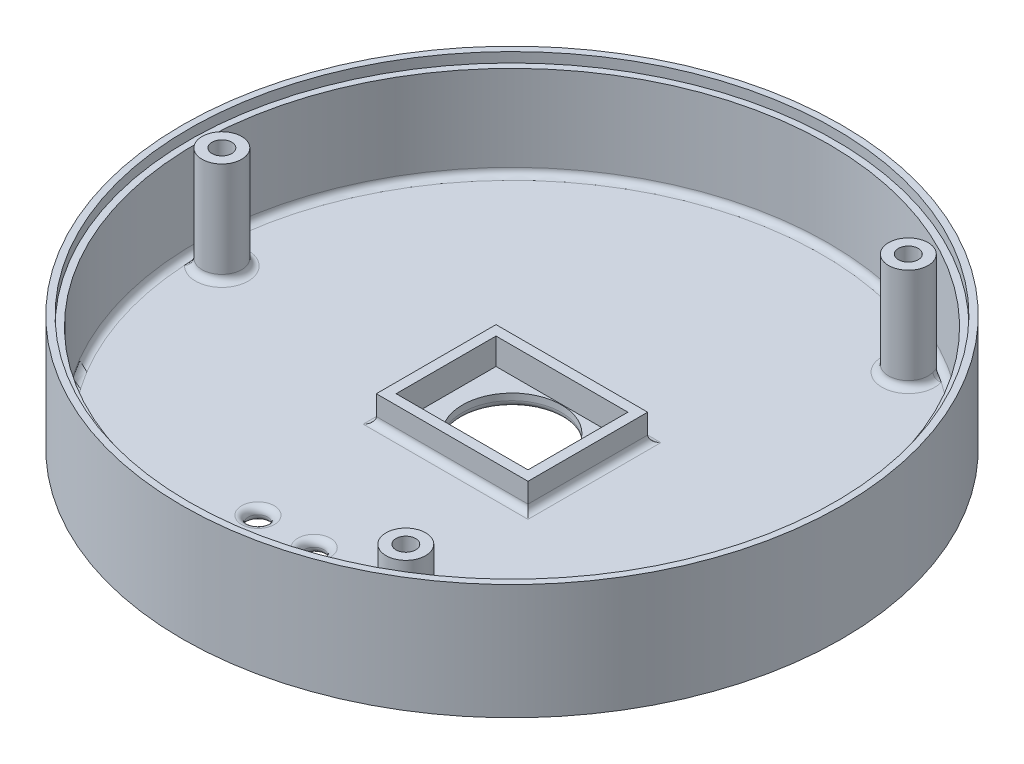
SolidWorks part; units mm, degrees
ref_plane "Front" through (0, 0, 0) normal (0, 0, 1) x (1, 0, 0)
ref_plane "Top" through (0, 0, 0) normal (0, 1, 0) x (1, 0, 0)
ref_plane "Right" through (0, 0, 0) normal (1, 0, 0) x (0, 0, -1)
sketch "Sketch1" plane through (0, 0, 0) normal (0, 1, 0) x (1, 0, 0)
  circle A0 centre (0, 0) radius 50
  dimension "D1" = 100
extrude "Boss-Extrude1" add sketch "Sketch1" along normal blind 17.5
shell "Shell1" thickness 2 removed face at (0, 17.5, 50)
sketch "Sketch13" plane through (0, 0, 0) normal (0, -1, 0) x (1, 0, 0)
  line L0 (0, 0) -> (0, 50) construction
  line L1 (-22.7742, 30) -> (22.7742, 30) construction
  line L2 (-22.7742, 34.5) -> (22.7742, 34.5) construction
  line L3 (-10, 30) -> (-10, 42.9485) construction
  line L6 (10, 30) -> (10, 41.7746) construction
  line L7 (-8.525, 30) -> (0, 30) construction
  line L8 (0, 30) -> (8.525, 30) construction
  circle A0 centre (0, 0) radius 50 construction
  circle A1 centre (0, 30) radius 1.475
  circle A2 centre (-8.525, 30) radius 1.475
  circle A3 centre (8.525, 30) radius 1.475
  circle A4 centre (0, 0) radius 7.5
  text T0 "<b> P      T     H</b>" font "Century Gothic" height 6.35
  point P9 (0, 30)
  point P20 (0, 34.5)
  dimension "D1" = 2.95
  dimension "D2" = 15
  dimension "D3" = 20
  dimension "D4" = 20
  dimension "D5" = 4.5
extrude "Cut-Extrude7" cut sketch "Sketch13" against normal blind 1
extrude "Cut-Extrude8" cut sketch "Sketch13<5>" against normal through all contours A2 | A1 | A3 | A4 region at (0, 0, 30) region at (-8.525, 0, 30) region at (8.525, 0, 30) region at (0, 0, 0)
sketch "Sketch13<5>" plane through (0, 0, 0) normal (0, -1, 0) x (1, 0, 0) same geometry as "Sketch13"
sketch "Sketch14" plane through (0, 17.5, 0) normal (0, 1, 0) x (1, 0, 0)
  circle A0 centre (0, 0) radius 49
  circle A1 centre (0, 0) radius 48
  circle A2 centre (0, 0) radius 48 construction
  dimension "D1" = 1
extrude "Cut-Extrude9" cut sketch "Sketch14" against normal blind 1.5
fillet "Fillet1" radius 1 4 edges at (0, 0, -7.5) (8.525, 0, 28.525) (0, 0, 28.525) (-8.525, 0, 28.525)
sketch "Sketch15" plane through (0, 2, 0) normal (0, 1, 0) x (1, 0, 0)
  line L0 (0, 0) -> (0, -23.7703) construction
  line L5 (7.5, 0) -> (-7.5, 0) construction
  line L7 (10, 7.575) -> (-10, 7.575)
  line L8 (10, 7.575) -> (10, -7.575)
  line L9 (10, -7.575) -> (-10, -7.575)
  line L10 (-10, 7.575) -> (-10, -7.575)
  line L11 (10, 7.575) -> (-10, -7.575) construction
  line L12 (10, -7.575) -> (-10, 7.575) construction
  line L13 (11.5, 9.075) -> (-11.5, 9.075)
  line L14 (11.5, 9.075) -> (11.5, -9.075)
  line L15 (11.5, -9.075) -> (-11.5, -9.075)
  line L16 (-11.5, 9.075) -> (-11.5, -9.075)
  line L17 (11.5, 9.075) -> (-11.5, -9.075) construction
  line L18 (11.5, -9.075) -> (-11.5, 9.075) construction
  circle A0 centre (0, 0) radius 7.5 construction
  point P0 (0, 0)
  point P13 (0, 0)
  dimension "D1" = 20
  dimension "D2" = 15.15
  dimension "D3" = 1.5
  dimension "D4" = 1.5
extrude "Boss-Extrude3" add sketch "Sketch15" along normal blind 4
fillet "Fillet2" radius 1 8 edges at (11.5, 2, 0) (0, 2, -9.075) (-11.5, 2, 0) (0, 2, 9.075) (0, 2, 48) (8.525, 2, 31.475) (0, 2, 31.475) (-8.525, 2, 31.475)
sketch "Sketch16" plane through (0, 2, 0) normal (0, 1, 0) x (1, 0, 0)
  line L0 (0, 0) -> (-44, 0) construction
  circle A0 centre (-44, 0) radius 3
  circle A1 centre (-44, 0) radius 1.5
  circle A2 centre (22, 38.1051) radius 3
  circle A3 centre (22, 38.1051) radius 1.5
  circle A4 centre (22, -38.1051) radius 3
  circle A5 centre (22, -38.1051) radius 1.5
  point P3 (0, 0)
  point P7 (-31.8782, -30.3279)
  point P8 (-43.2436, -8.1237)
  point P15 (0, 0)
  dimension "D2" = 6
  dimension "D3" = 3
  dimension "D1" = 44
  dimension "D4" = 3
extrude "Boss-Extrude4" add sketch "Sketch16" along normal up to surface (15.5 mm away) up to face at (0, 17.5, 49)
fillet "Fillet3" radius 1 3 edges at (22, 2, -35.1051) (22, 2, 41.1051) (-44, 2, 3)
equation "\"Outer Diameter\"= 100"
equation "\"Wall Thickness\"= 2"
equation "\"Cylinder Height\"= 20 - 2.5"
equation "\"Pin Distance\"= 30'Distance from wall to the barrels jack retaining pin"
equation "\"Pin Spacing\"= 10.2'Distance between barrel jack retaining pins"
equation "\"Pin Length\"= 4"
equation "\"Pin Width\"= 2"
equation "\"Switching Board Width\"= 23.5"
equation "\"Switching Board Length\"= 31.3"
equation "\"Nano Length\"= 45"
equation "\"Nano Width\"= 18"
equation "\"Buck Length\"= 44"
equation "\"Buck Width\"= 21.3"
equation "\"D1@Sketch1\"=\"Outer Diameter\""
equation "\"D1@Shell1\"=\"Wall Thickness\""
equation "\"DHT Width\"= 22"
equation "\"DHT Length\"= 40"
equation "\"D1@Boss-Extrude1\"=\"Cylinder Height\""
